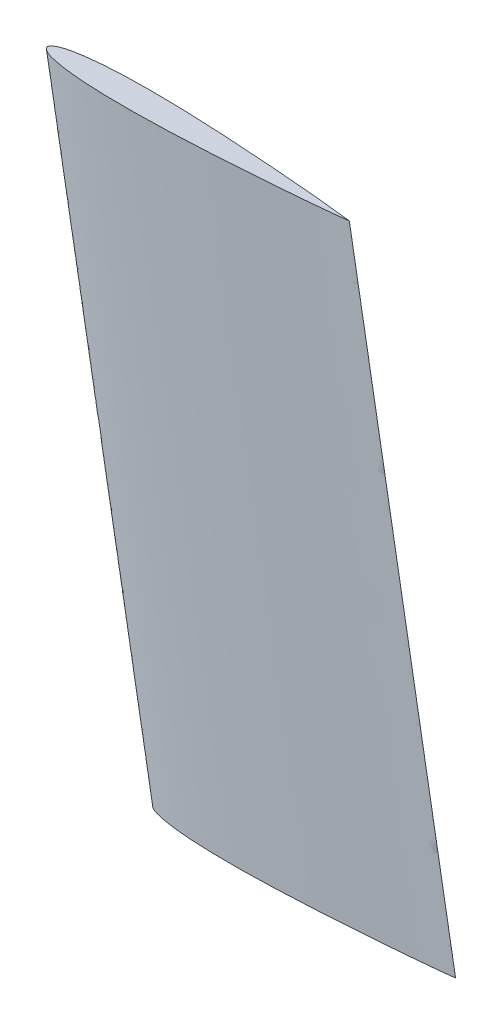
SolidWorks part; units mm, degrees
ref_plane "Front Plane" through (0, 0, 0) normal (0, 0, 1) x (1, 0, 0)
ref_plane "Top Plane" through (0, 0, 0) normal (0, 1, 0) x (1, 0, 0)
ref_plane "Right Plane" through (0, 0, 0) normal (1, 0, 0) x (0, 0, -1)
curve "Curve2"
  spline degree 3 poles (245.7346, 0, -0.2359) (248.5694, 0, 0) (245.7346, 0, 0.2359) (243.4112, 0, 0.6292) (237.7674, 0, 1.2323) (230.8332, 0, 1.9808) (221.7981, 0, 2.8592) (211.1903, 0, 3.8286) (199.0563, 0, 4.8702) (185.65, 0, 5.9536) (171.1852, 0, 7.0355) (155.914, 0, 8.0839) (140.0967, 0, 9.0504) (124.0041, 0, 9.8942) (107.9109, 0, 10.5652) (94.6227, 0, 10.9527) (84.1989, 0, 11.1308) (76.6156, 0, 11.194) (69.2347, 0, 11.1852) (62.0877, 0, 11.0901) (55.2058, 0, 10.9234) (48.6191, 0, 10.6715) (42.3552, 0, 10.3437) (36.4402, 0, 9.9323) (30.8991, 0, 9.4444) (25.7573, 0, 8.8756) (21.0365, 0, 8.2367) (16.7549, 0, 7.5443) (12.9305, 0, 6.8014) (9.5757, 0, 6.0106) (6.7064, 0, 5.1453) (4.3287, 0, 4.1895) (2.4645, 0, 3.1349) (1.1239, 0, 2.0336) (0.2866, 0, 1.0243) (-0.1173, 0, 0) (0.2866, 0, -1.0243) (1.1239, 0, -2.0336) (2.4645, 0, -3.1349) (4.3287, 0, -4.1895) (6.7064, 0, -5.1453) (9.5757, 0, -6.0106) (12.9305, 0, -6.8014) (16.7549, 0, -7.5443) (21.0365, 0, -8.2367) (25.7573, 0, -8.8756) (30.8991, 0, -9.4444) (36.4402, 0, -9.9323) (42.3552, 0, -10.3437) (48.6191, 0, -10.6715) (55.2058, 0, -10.9234) (62.0877, 0, -11.0901) (69.2347, 0, -11.1852) (76.6156, 0, -11.194) (84.1989, 0, -11.1308) (94.6227, 0, -10.9527) (107.9109, 0, -10.5652) (124.0041, 0, -9.8942) (140.0967, 0, -9.0504) (155.914, 0, -8.0839) (171.1852, 0, -7.0355) (185.65, 0, -5.9536) (199.0563, 0, -4.8702) (211.1903, 0, -3.8286) (221.7981, 0, -2.8592) (230.8332, 0, -1.9808) (237.7674, 0, -1.2323) (243.4112, 0, -0.6292) (245.7346, 0, -0.2359) (248.5694, 0, 0) (245.7346, 0, 0.2359) knots -0.018944 -0.008488 -0.002133 0 0.002133 0.008488 0.018944 0.033319 0.051356 0.072756 0.097141 0.124097 0.153163 0.183834 0.215589 0.247878 0.280151 0.31186 0.327333 0.342463 0.357187 0.371448 0.385183 0.398331 0.410845 0.422673 0.433769 0.44409 0.453589 0.46224 0.47001 0.476871 0.482833 0.487909 0.492155 0.495592 0.498196 0.5 0.501804 0.504408 0.507845 0.512091 0.517167 0.523129 0.52999 0.53776 0.546411 0.55591 0.566231 0.577327 0.589155 0.601669 0.614817 0.628552 0.642813 0.657537 0.672667 0.68814 0.719849 0.752122 0.784411 0.816166 0.846837 0.875903 0.902859 0.927244 0.948644 0.966681 0.981056 0.991512 0.997867 1 1.002133 1.008488 1.018944 periodic
sketch "Sketch6" plane through (0, 0, 0) normal (0, 1, 0) x (1, 0, 0)
  spline S0 degree 3 poles (245.7346, -0.2359) (248.5694, 0) (245.7346, 0.2359) (243.4112, 0.6292) (237.7674, 1.2323) (230.8332, 1.9808) (221.7981, 2.8592) (211.1903, 3.8286) (199.0563, 4.8702) (185.65, 5.9536) (171.1852, 7.0355) (155.914, 8.0839) (140.0967, 9.0504) (124.0041, 9.8942) (107.9109, 10.5652) (94.6227, 10.9527) (84.1989, 11.1308) (76.6156, 11.194) (69.2347, 11.1852) (62.0877, 11.0901) (55.2058, 10.9234) (48.6191, 10.6715) (42.3552, 10.3437) (36.4402, 9.9323) (30.8991, 9.4444) (25.7573, 8.8756) (21.0365, 8.2367) (16.7549, 7.5443) (12.9305, 6.8014) (9.5757, 6.0106) (6.7064, 5.1453) (4.3287, 4.1895) (2.4645, 3.1349) (1.1239, 2.0336) (0.2866, 1.0243) (-0.1173, 0) (0.2866, -1.0243) (1.1239, -2.0336) (2.4645, -3.1349) (4.3287, -4.1895) (6.7064, -5.1453) (9.5757, -6.0106) (12.9305, -6.8014) (16.7549, -7.5443) (21.0365, -8.2367) (25.7573, -8.8756) (30.8991, -9.4444) (36.4402, -9.9323) (42.3552, -10.3437) (48.6191, -10.6715) (55.2058, -10.9234) (62.0877, -11.0901) (69.2347, -11.1852) (76.6156, -11.194) (84.1989, -11.1308) (94.6227, -10.9527) (107.9109, -10.5652) (124.0041, -9.8942) (140.0967, -9.0504) (155.914, -8.0839) (171.1852, -7.0355) (185.65, -5.9536) (199.0563, -4.8702) (211.1903, -3.8286) (221.7981, -2.8592) (230.8332, -1.9808) (237.7674, -1.2323) (243.4112, -0.6292) (245.7346, -0.2359) (248.5694, 0) (245.7346, 0.2359) knots -0.018944 -0.008488 -0.002133 0 0.002133 0.008488 0.018944 0.033319 0.051356 0.072756 0.097141 0.124097 0.153163 0.183834 0.215589 0.247878 0.280151 0.31186 0.327333 0.342463 0.357187 0.371448 0.385183 0.398331 0.410845 0.422673 0.433769 0.44409 0.453589 0.46224 0.47001 0.476871 0.482833 0.487909 0.492155 0.495592 0.498196 0.5 0.501804 0.504408 0.507845 0.512091 0.517167 0.523129 0.52999 0.53776 0.546411 0.55591 0.566231 0.577327 0.589155 0.601669 0.614817 0.628552 0.642813 0.657537 0.672667 0.68814 0.719849 0.752122 0.784411 0.816166 0.846837 0.875903 0.902859 0.927244 0.948644 0.966681 0.981056 0.991512 0.997867 1 1.002133 1.008488 1.018944 only from (248, 0) to (248, 0) construction
  spline S1 degree 3 poles (245.7346, -0.2359) (248.5694, 0) (245.7346, 0.2359) (243.4112, 0.6292) (237.7674, 1.2323) (230.8332, 1.9808) (221.7981, 2.8592) (211.1903, 3.8286) (199.0563, 4.8702) (185.65, 5.9536) (171.1852, 7.0355) (155.914, 8.0839) (140.0967, 9.0504) (124.0041, 9.8942) (107.9109, 10.5652) (94.6227, 10.9527) (84.1989, 11.1308) (76.6156, 11.194) (69.2347, 11.1852) (62.0877, 11.0901) (55.2058, 10.9234) (48.6191, 10.6715) (42.3552, 10.3437) (36.4402, 9.9323) (30.8991, 9.4444) (25.7573, 8.8756) (21.0365, 8.2367) (16.7549, 7.5443) (12.9305, 6.8014) (9.5757, 6.0106) (6.7064, 5.1453) (4.3287, 4.1895) (2.4645, 3.1349) (1.1239, 2.0336) (0.2866, 1.0243) (-0.1173, 0) (0.2866, -1.0243) (1.1239, -2.0336) (2.4645, -3.1349) (4.3287, -4.1895) (6.7064, -5.1453) (9.5757, -6.0106) (12.9305, -6.8014) (16.7549, -7.5443) (21.0365, -8.2367) (25.7573, -8.8756) (30.8991, -9.4444) (36.4402, -9.9323) (42.3552, -10.3437) (48.6191, -10.6715) (55.2058, -10.9234) (62.0877, -11.0901) (69.2347, -11.1852) (76.6156, -11.194) (84.1989, -11.1308) (94.6227, -10.9527) (107.9109, -10.5652) (124.0041, -9.8942) (140.0967, -9.0504) (155.914, -8.0839) (171.1852, -7.0355) (185.65, -5.9536) (199.0563, -4.8702) (211.1903, -3.8286) (221.7981, -2.8592) (230.8332, -1.9808) (237.7674, -1.2323) (243.4112, -0.6292) (245.7346, -0.2359) (248.5694, 0) (245.7346, 0.2359) knots -0.018944 -0.008488 -0.002133 0 0.002133 0.008488 0.018944 0.033319 0.051356 0.072756 0.097141 0.124097 0.153163 0.183834 0.215589 0.247878 0.280151 0.31186 0.327333 0.342463 0.357187 0.371448 0.385183 0.398331 0.410845 0.422673 0.433769 0.44409 0.453589 0.46224 0.47001 0.476871 0.482833 0.487909 0.492155 0.495592 0.498196 0.5 0.501804 0.504408 0.507845 0.512091 0.517167 0.523129 0.52999 0.53776 0.546411 0.55591 0.566231 0.577327 0.589155 0.601669 0.614817 0.628552 0.642813 0.657537 0.672667 0.68814 0.719849 0.752122 0.784411 0.816166 0.846837 0.875903 0.902859 0.927244 0.948644 0.966681 0.981056 0.991512 0.997867 1 1.002133 1.008488 1.018944 only from (248, 0) to (248, 0)
ref_plane "Plane4" through (0, 495, 0) normal (0, 1, 0) x (1, 0, 0)
sketch "Sketch8" plane through (0, 0, 0) normal (0, 0, 1) x (1, 0, 0)
  line L0 (0, 0) -> (-87.2819, 495)
  line L1 (248, 0) -> (160.7181, 495)
  line L2 (248, 0) -> (0, 0) construction
  dimension "D1" = 80
  dimension "D2" = 80
  dimension "D3" = 495
  dimension "D4" = 495
sketch "Sketch9" plane through (0, 495, 0) normal (0, 1, 0) x (1, 0, 0)
  spline S2 degree 3 poles (158.4527, -0.2359) (161.2875, 0) (158.4527, 0.2359) (156.1293, 0.6292) (150.4855, 1.2323) (143.5514, 1.9808) (134.5162, 2.8592) (123.9084, 3.8286) (111.7744, 4.8702) (98.3682, 5.9536) (83.9033, 7.0355) (68.6322, 8.0839) (52.8148, 9.0504) (36.7222, 9.8942) (20.6291, 10.5652) (7.3409, 10.9527) (-3.0829, 11.1308) (-10.6663, 11.194) (-18.0472, 11.1852) (-25.1942, 11.0901) (-32.076, 10.9234) (-38.6627, 10.6715) (-44.9266, 10.3437) (-50.8417, 9.9323) (-56.3828, 9.4444) (-61.5245, 8.8756) (-66.2454, 8.2367) (-70.5269, 7.5443) (-74.3513, 6.8014) (-77.7061, 6.0106) (-80.5755, 5.1453) (-82.9532, 4.1895) (-84.8174, 3.1349) (-86.158, 2.0336) (-86.9952, 1.0243) (-87.3992, 0) (-86.9952, -1.0243) (-86.158, -2.0336) (-84.8174, -3.1349) (-82.9532, -4.1895) (-80.5755, -5.1453) (-77.7061, -6.0106) (-74.3513, -6.8014) (-70.5269, -7.5443) (-66.2454, -8.2367) (-61.5245, -8.8756) (-56.3828, -9.4444) (-50.8417, -9.9323) (-44.9266, -10.3437) (-38.6627, -10.6715) (-32.076, -10.9234) (-25.1942, -11.0901) (-18.0472, -11.1852) (-10.6663, -11.194) (-3.0829, -11.1308) (7.3409, -10.9527) (20.6291, -10.5652) (36.7222, -9.8942) (52.8148, -9.0504) (68.6322, -8.0839) (83.9033, -7.0355) (98.3682, -5.9536) (111.7744, -4.8702) (123.9084, -3.8286) (134.5162, -2.8592) (143.5514, -1.9808) (150.4855, -1.2323) (156.1293, -0.6292) (158.4527, -0.2359) (161.2875, 0) (158.4527, 0.2359) knots -0.018944 -0.008488 -0.002133 0 0.002133 0.008488 0.018944 0.033319 0.051356 0.072756 0.097141 0.124097 0.153163 0.183834 0.215589 0.247878 0.280151 0.31186 0.327333 0.342463 0.357187 0.371448 0.385183 0.398331 0.410845 0.422673 0.433769 0.44409 0.453589 0.46224 0.47001 0.476871 0.482833 0.487909 0.492155 0.495592 0.498196 0.5 0.501804 0.504408 0.507845 0.512091 0.517167 0.523129 0.52999 0.53776 0.546411 0.55591 0.566231 0.577327 0.589155 0.601669 0.614817 0.628552 0.642813 0.657537 0.672667 0.68814 0.719849 0.752122 0.784411 0.816166 0.846837 0.875903 0.902859 0.927244 0.948644 0.966681 0.981056 0.991512 0.997867 1 1.002133 1.008488 1.018944 only from (160.7181, 0) to (160.7181, 0)
loft "Loft1" add profiles "Sketch6", "Sketch9" connector at (248, 0, 0) connector at (160.7181, 495, 0)
